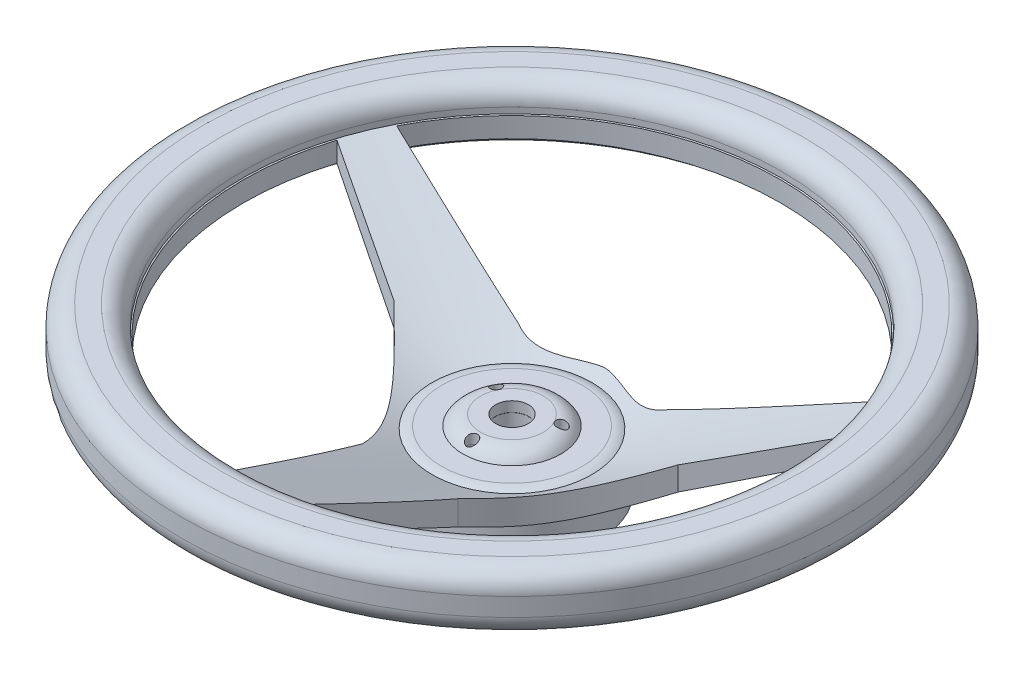
SolidWorks part; units mm, degrees
material "ABS PC"
ref_plane "Front Plane" through (0, 0, 0) normal (0, 0, 1) x (1, 0, 0)
ref_plane "Top Plane" through (0, 0, 0) normal (0, 1, 0) x (1, 0, 0)
ref_plane "Right Plane" through (0, 0, 0) normal (1, 0, 0) x (0, 0, -1)
sketch "Sketch1" plane through (0, 0, 0) normal (0, 1, 0) x (1, 0, 0)
  circle A0 centre (0, 0) radius 162.5
extrude "Boss-Extrude1" add sketch "Sketch1" along normal blind 80
sketch "Sketch2" plane through (0, 80, 0) normal (0, 1, 0) x (1, 0, 0)
  line L0 (-117.7131, 60.8266) -> (-36.6743, 40)
  line L1 (-126.3181, 40) -> (-70.063, 11.8709)
  line L2 (-23.4898, -50.0926) -> (-13.5255, -131.8079)
  line L5 (23.4898, -50.0926) -> (13.5255, -131.8079)
  line L6 (126.3181, 40) -> (70.063, 11.8709)
  line L7 (117.7131, 60.8266) -> (36.6743, 40)
  arc A0 (-117.7131, 60.8266) -> (-126.3181, 40) centre (0, 0) ccw
  circle A1 centre (0, 0) radius 40
  circle A2 centre (0, 0) radius 8
  circle A3 centre (0, -19.653) radius 2.7614
  circle A4 centre (16.154, 8.3265) radius 2.7614
  circle A5 centre (-16.154, 8.3265) radius 2.7614
  arc A6 (-126.3181, 40) -> (-13.5255, -131.8079) centre (0, 0) ccw
  arc A7 (117.7131, 60.8266) -> (-117.7131, 60.8266) centre (0, 0) ccw
  arc A8 (126.3181, 40) -> (117.7131, 60.8266) centre (0, 0) ccw
  arc A9 (13.5255, -131.8079) -> (126.3181, 40) centre (0, 0) ccw
  arc A10 (-13.5255, -131.8079) -> (13.5255, -131.8079) centre (0, 0) ccw
  spline S0 degree 3 poles (-36.6743, 40) (-24.1423, 34.5312) (-12.2609, 45.1849) (0, 46.0063) knots 0 0 0 0 1 1 1 1
  spline S1 degree 3 poles (-70.063, 11.8709) (-51.5216, -6.4411) (-32.4312, -23.8238) (-23.4898, -50.0926) knots 0 0 0 0 1 1 1 1
  spline S2 degree 3 poles (70.063, 11.8709) (51.5216, -6.4411) (32.4312, -23.8238) (23.4898, -50.0926) knots 0 0 0 0 1 1 1 1
  spline S3 degree 3 poles (36.6743, 40) (24.1423, 34.5312) (12.2609, 45.1849) (0, 46.0063) knots 0 0 0 0 1 1 1 1
  point P36 (0, -1)
  dimension "D1" = 3
extrude "Cut-Extrude1" cut sketch "Sketch2" against normal blind 80 and the other way blind 1 contours S3 L7 A0 L0 S0 | L6 S2 L5 A0 | S1 L1 A0 L2 | A2 | A3 | A5 | A4 region at (0, 80, -82.5366) region at (-74.5114, 80, 47.9548) region at (74.5114, 80, 47.9548) region at (0, 80, 0) region at (0, 80, 19.653) region at (16.154, 80, -8.3265) region at (-16.154, 80, -8.3265)
extrude "Cut-Extrude2" cut sketch "Sketch2<3>" against normal blind 52 and the other way blind 11 contours A1 A5 A4 A3 A2 region at (-38.8686, 80, 0)
sketch "Sketch2<3>" plane through (0, 80, 0) normal (0, 1, 0) x (1, 0, 0) same geometry as "Sketch2"
sketch "Sketch3" plane through (0, 0, 0) normal (1, 0, 0) x (0, 0, -1)
  line L0 (-132.5, 51.0289) -> (-162.5, 51.0289)
  line L5 (-162.5, 51.0289) -> (-162.5, 0)
  line L6 (-162.5, 0) -> (-132.5, 0)
  line L7 (-132.5, 0) -> (-132.5, 51.0289)
ref_axis "Axis1" through (0, 0, 0) along (0, 1, 0)
revolve "Cut-Revolve3" cut sketch "Sketch3" angle 360 about axis through (0, 0, 0) along (0, 1, 0)
fillet "Fillet1" radius 10 1 edges at (0, 80, 162.5)
fillet "Fillet2" radius 10 1 edges at (0, 51.0289, -162.5)
sketch "Sketch10" plane through (0, 0, 0) normal (0, -1, 0) x (1, 0, 0)
  circle A0 centre (0, 0) radius 38.6786
  circle A1 centre (0, 0) radius 21.8134
extrude "Cut-Extrude4" cut sketch "Sketch10" against normal blind 20
sketch "Sketch11" plane through (0, 0, 0) normal (0, -1, 0) x (1, 0, 0)
  circle A0 centre (0, 0) radius 18.4505
extrude "Cut-Extrude5" cut sketch "Sketch11" against normal blind 20
sketch "Sketch12" plane through (0, 0, 0) normal (0, 0, 1) x (1, 0, 0)
  line L0 (-126.3181, -0.0461) -> (-42.2793, -0.0163)
  line L2 (-42.2793, 15.66) -> (-133.9189, 57.5681)
  line L3 (-133.9189, 57.5681) -> (-133.9189, -0.0461)
  line L4 (-133.9189, -0.0461) -> (-126.3181, -0.0461)
  line L5 (-42.2793, 15.66) -> (-42.2793, -0.0163)
revolve "Cut-Revolve6" cut sketch "Sketch12" angle 360 about axis through (0, 0, 0) along (0, 1, 0)
sketch "Sketch13" plane through (0, 0, 0) normal (0, 0, 1) x (1, 0, 0)
  line L1 (-39.3714, 26.8271) -> (-133.1401, 67.0933)
  line L2 (-39.3714, 26.8271) -> (-39.3714, 80.0279)
  line L3 (-39.3714, 80.0279) -> (-133.1401, 80.0279)
  line L4 (-133.1401, 80.0279) -> (-133.1401, 67.0933)
revolve "Cut-Revolve8" cut sketch "Sketch13" angle 360 about axis through (0, 0, 0) along (0, 1, 0)
fillet "Fillet3" radius 10 1 edges at (0, 80, 133.1401)
fillet "Fillet4" radius 10 1 edges at (0, 51.0289, -133.9189)
fillet "Fillet5" radius 10 1 edges at (0, 28, 39.3714)
sketch "Sketch14" plane through (0, 0, 0) normal (0, 1, 0) x (1, 0, 0)
  circle A0 centre (-16.154, 8.3265) radius 6
  circle A1 centre (16.154, 8.3265) radius 6
  circle A2 centre (0, -19.653) radius 6
  point P8 (0, -1)
  dimension "D1" = 3
extrude "Boss-Extrude4" add sketch "Sketch14" along normal blind 20
sketch "Sketch16" plane through (0, 0, 0) normal (0, -1, 0) x (-1, 0, 0)
  circle A0 centre (0, -19.653) radius 2.76
  circle A1 centre (-16.154, 8.3265) radius 2.76
  circle A2 centre (16.154, 8.3265) radius 2.76
  point P8 (0, -1)
  dimension "D1" = 3
extrude "Cut-Extrude6" cut sketch "Sketch16" against normal blind 70
sketch "Sketch17" plane through (0, 28, 0) normal (0, 1, 0) x (1, 0, 0)
  circle A0 centre (0, 0) radius 24.1349
extrude "Boss-Extrude6" add sketch "Sketch17" along normal blind 5 separate body
sketch "Sketch18" plane through (0, 33, 0) normal (0, 1, 0) x (1, 0, 0)
  circle A0 centre (0, 0) radius 8.0952
  circle A1 centre (0, -19.653) radius 2.6724
  circle A2 centre (-16.154, 8.3265) radius 2.6724
  circle A3 centre (16.154, 8.3265) radius 2.6724
  point P10 (0, -1)
  dimension "D1" = 3
extrude "Cut-Extrude7" cut sketch "Sketch18" against normal blind 5
fillet "Fillet6" radius 10 1 edges at (0, 33, 24.1349)
